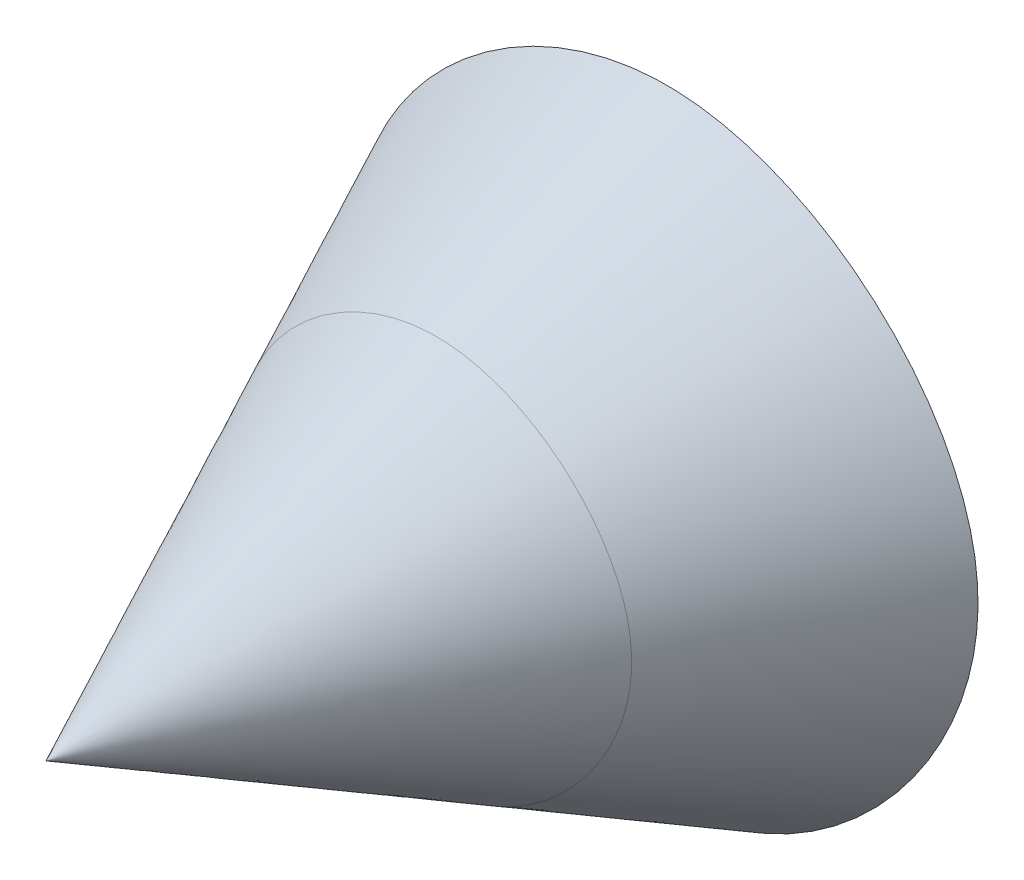
SolidWorks part; units mm, degrees
other "Camera2"
other "Markup1"
sketch "Sketch9" [suppressed] plane through (62.8636, 53.3376, 108.883) normal (1, 0, 0) x (0, 0, 1)
sketch "Sketch10" plane through (62.8636, 53.3376, 108.883) normal (1, 0, 0) x (0, 0, 1)
sketch "Sketch11" [suppressed] plane through (62.8636, 53.3376, 109.299) normal (1, 0, 0) x (0, 0, 1)
sketch "Sketch12" [suppressed] plane through (54.313, 46.6008, 109.299) normal (1, 0, 0) x (0, 0, 1)
sketch "Sketch13" plane through (62.8636, 53.3376, 108.883) normal (1, 0, 0) x (0, 0, 1)
sketch "Sketch14" plane through (54.9764, 28.7192, 107.6385) normal (1, 0, 0) x (0, 0, 1)
ref_plane "Front Plane" through (0, 0, 0) normal (0, 0, 1) x (1, 0, 0)
ref_plane "Top Plane" through (0, 0, 0) normal (0, 1, 0) x (1, 0, 0)
ref_plane "Right Plane" through (0, 0, 0) normal (1, 0, 0) x (0, 0, -1)
sketch "Sketch1" plane through (0, 0, 0) normal (1, 0, 0) x (0, 0, -1)
  line L0 (0, 0) -> (-68.9166, 0) construction
  line L1 (-2.1532, 12.2116) -> (-107.6384, -18.9795)
  line L2 (-107.6384, -18.9795) -> (0, 0)
  line L3 (0, 0) -> (-2.1532, 12.2116)
  point P8 (-2.1532, 12.2116)
  point P11 (0, 0)
  dimension "D1" = 12.4
  dimension "D2" = 110
  dimension "pitch" = 10
ref_plane "Plane1" through (0, 0, 0) normal (0, 0.9848, 0.1736) x (1, 0, 0)
sketch "Sketch2" plane through (0, 0, 0) normal (0, 0.9848, 0.1736) x (1, 0, 0)
  line L0 (0, -109.2989) -> (-34, 0)
  line L1 (0, -109.2989) -> (0, 0) construction
  line L2 (-34, 0) -> (34, 0)
  line L3 (34, 0) -> (0, -109.2989)
  point P8 (0, 0)
  dimension "D1" = 68
sketch "Sketch3" plane through (0, 0, 0) normal (1, 0, 0) x (0, 0, -1)
  point P0 (-2.1532, 12.2116)
loft "Loft1" add profiles "Sketch3", "Sketch2"
sketch "Sketch4" plane through (0, 0, 0) normal (1, 0, 0) x (0, 0, -1)
  line L0 (-107.6384, -18.9795) -> (0, 28.7192)
  line L1 (-107.6384, -18.9795) -> (0, -78.8903)
  line L2 (200000, 0) -> (-200068.9166, 0) construction
  dimension "top_angle" = 29.1
  dimension "bottom_angle" = 23.9
ref_plane "Plane2" through (0, -18.9795, 0) normal (0, 1, 0) x (1, 0, 0)
sketch "Sketch6" plane through (0, -18.9795, 0) normal (0, 1, 0) x (1, 0, 0)
  line L0 (0, -107.6384) -> (53.9013, 0)
  line L1 (0, -107.6384) -> (-53.9013, 0)
  line L2 (0, -2.1532) -> (0, -107.6384) construction
  line L3 (0, -107.6384) -> (0, 0) construction
  dimension "left" = 26.6
  dimension "right" = 26.6
sketch "Sketch7" plane through (0, 0, 0) normal (0, 0, 1) x (1, 0, 0)
  line L0 (0, -18.9795) -> (0, -78.8903) construction
  line L1 (59.7443, -18.9795) -> (-59.7443, -18.9795) construction
  line L2 (0, -18.9795) -> (0, 28.7192) construction
  line L3 (0, -18.9795) -> (53.9013, -18.9795) construction
  spline S0 degree 3 poles (81.0817, -18.9294) (0, -110.5634) (-81.0817, -18.9294) (0, 51.1984) (81.0817, -18.9294) (0, -110.5634) (-81.0817, -18.9294) knots -0.735885 -0.5 -0.264115 0 0.264115 0.5 0.735885 1 1.264115 1.5 1.735885 only from (0, -78.8903) to (0, -78.8903)
sketch "Sketch8" plane through (0, -18.9795, 0) normal (0, 1, 0) x (1, 0, 0)
  point P0 (0, -107.6384)
surface "Surface-Loft1"
ref_plane "Plane3" through (0, 0, 40) normal (0, 0, 1) x (1, 0, 0)
split line "Split Line1"
sketch "Sketch16" plane through (0, 0, 40) normal (0, 0, 1) x (1, 0, 0)
  line L0 (-30, -145.6127) -> (-30, -35.8854)
  line L1 (-30, -35.8854) -> (-24.8554, -33.201) construction
  line L2 (-30, -35.8854) -> (-25.8501, -43.8385) construction
  line L3 (0, -18.9795) -> (0, -78.8903) construction
  line L4 (-30, -35.8854) -> (-23.4657, 1.1726)
  line L5 (-23.4657, 1.1726) -> (-23.4657, 35.7217)
  spline S0 degree 3 poles (-32.4658, -12.3125) (-33.2148, -14.4752) (-37.4747, -34.1777) (0, -76.5295) (50.9506, -18.948) (2.3392, 23.0961) (-27.9856, 0.6246) (-32.4658, -12.3125) (-33.2148, -14.4752) (-37.4747, -34.1777) knots -0.2021 0 0 0 0.033785 0.2979 0.562015 0.7979 1 1 1 1.033785 1.2979 1.562015 only from (-32.4658, -12.3125) to (-32.4658, -12.3125) construction
  dimension "D1" = 30
  dimension "D2" = 52.445
  dimension "D3" = 62.445
equation "\"D2@Sketch16\"=\"D3@Sketch16\"-10"
